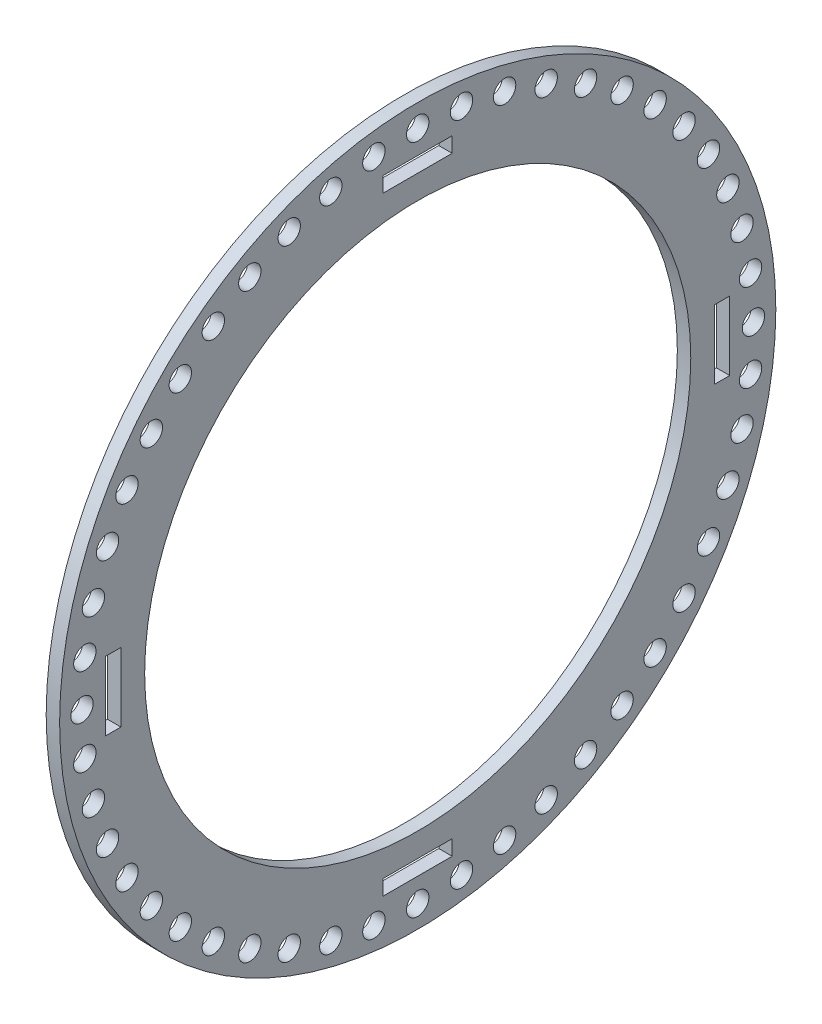
SolidWorks part; units mm, degrees
material "AISI 304"
ref_plane "Front Plane" through (0, 0, 0) normal (0, 0, 1) x (1, 0, 0)
ref_plane "Top Plane" through (0, 0, 0) normal (0, 1, 0) x (1, 0, 0)
ref_plane "Right Plane" through (0, 0, 0) normal (1, 0, 0) x (0, 0, -1)
sketch "Sketch1" plane through (0, 0, 0) normal (1, 0, 0) x (0, 0, -1)
  line L0 (0, 0) -> (0, 40) construction
  line L62 (-3.85, 34.85) -> (3.85, 34.85)
  line L63 (-3.85, 34.85) -> (-3.85, 33.15)
  line L64 (-3.85, 33.15) -> (3.85, 33.15)
  line L65 (3.85, 34.85) -> (3.85, 33.15)
  line L66 (-3.85, 34.85) -> (3.85, 33.15) construction
  line L67 (-3.85, 33.15) -> (3.85, 34.85) construction
  line L103 (34.85, 3.85) -> (34.85, -3.85)
  line L104 (33.15, 3.85) -> (33.15, -3.85)
  line L105 (34.85, 3.85) -> (33.15, 3.85)
  line L106 (34.85, -3.85) -> (33.15, -3.85)
  line L107 (3.85, -34.85) -> (-3.85, -34.85)
  line L108 (3.85, -33.15) -> (-3.85, -33.15)
  line L109 (3.85, -34.85) -> (3.85, -33.15)
  line L110 (-3.85, -34.85) -> (-3.85, -33.15)
  line L111 (-34.85, -3.85) -> (-34.85, 3.85)
  line L112 (-33.15, -3.85) -> (-33.15, 3.85)
  line L113 (-34.85, -3.85) -> (-33.15, -3.85)
  line L114 (-34.85, 3.85) -> (-33.15, 3.85)
  circle A3 centre (0, 0) radius 40
  circle A25 centre (0, 0) radius 30.5
  point P9 (0, -20)
  point P11 (-20, 0)
  point P22 (0, 34)
  point P29 (20, 0)
  point P31 (0, 30)
  point P75 (0, 0)
  point P81 (0, -1)
  point P93 (0, 0)
  point P95 (0, 0)
  dimension "D2" = 80
  dimension "D3" = 61
  dimension "D7" = 7.7
  dimension "D8" = 1.7
  dimension "D9" = 10
  dimension "D12" = 6
  dimension "D14" = 4
extrude "Boss-Extrude4" add sketch "Sketch1" along normal blind 1.5
sketch "Sketch2" plane through (1.5, 0, 0) normal (1, 0, 0) x (0, 0, -1)
  circle A0 centre (0, 37.5) radius 1.25
  circle A1 centre (0, 0) radius 40 construction
  dimension "D2" = 2.5
  dimension "D1" = 37.5
extrude "Cut-Extrude2" cut sketch "Sketch2" against normal blind 1.5
pattern_circular "CirPattern3" count 48 over 360 about axis through (1.5, 0, 0) along (1, 0, 0) of "Cut-Extrude2"
